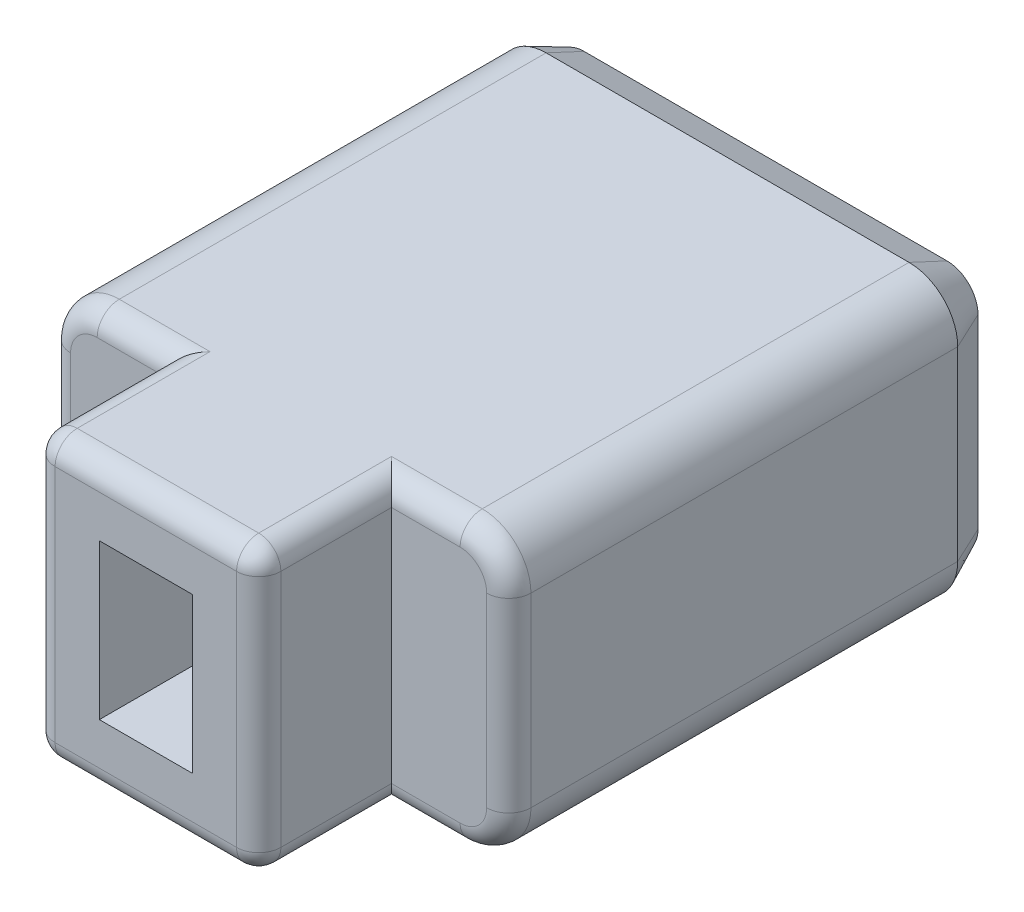
SolidWorks part; units mm, degrees
ref_plane "Plan de face" through (0, 0, 0) normal (0, 0, 1) x (1, 0, 0)
ref_plane "Plan de dessus" through (0, 0, 0) normal (0, 1, 0) x (1, 0, 0)
ref_plane "Plan de droite" through (0, 0, 0) normal (1, 0, 0) x (0, 0, -1)
sketch "Esquisse2" plane through (0, 0, 0) normal (0, 0, 1) x (1, 0, 0)
  line L1 (1.1, 0) -> (9.3, 0)
  line L2 (0, 1.1) -> (0, 5.3)
  line L3 (1.1, 6.4) -> (9.3, 6.4)
  line L4 (10.4, 1.1) -> (10.4, 5.3)
  arc A0 (9.3, 6.4) -> (10.4, 5.3) centre (9.3, 5.3) cw
  arc A1 (9.3, 0) -> (10.4, 1.1) centre (9.3, 1.1) ccw
  arc A2 (1.1, 0) -> (0, 1.1) centre (1.1, 1.1) cw
  arc A3 (0, 5.3) -> (1.1, 6.4) centre (1.1, 5.3) cw
  point P7 (10.4, 6.4)
  point P12 (0, 0)
  point P15 (0, 6.4)
  dimension "D3" = 1.1
  dimension "D1" = 10.4
  dimension "D2" = 6.4
extrude "Boss.-Extru.1" add sketch "Esquisse2" along normal blind 14
sketch "Esquisse3" plane through (0, 0, 14) normal (0, 0, 1) x (1, 0, 0)
  line L0 (0, 5.3) -> (0, 1.1) construction
  line L1 (4.15, 4.95) -> (6.25, 4.95)
  line L2 (4.15, 4.95) -> (4.15, 1.45)
  line L3 (4.15, 1.45) -> (6.25, 1.45)
  line L4 (6.25, 4.95) -> (6.25, 1.45)
  line L5 (10.4, 1.1) -> (10.4, 5.3) construction
  line L6 (9.3, 6.4) -> (1.1, 6.4) construction
  line L7 (1.1, 0) -> (9.3, 0) construction
  dimension "D1" = 2.1
  dimension "D2" = 3.5
  dimension "D3" = 4.15
  dimension "D4" = 4.15
  dimension "D5" = 1.45
  dimension "D6" = 1.45
extrude "Enlèv. mat.-Extru.1" cut sketch "Esquisse3" against normal blind 3
sketch "Esquisse4" plane through (0, 0, 14) normal (0, 0, 1) x (1, 0, 0)
  line L0 (2.65, 6.4) -> (2.65, 0)
  line L1 (9.3, 6.4) -> (1.1, 6.4) construction
  line L2 (1.1, 0) -> (9.3, 0) construction
  line L3 (2.65, 0) -> (7.75, 0)
  line L4 (7.75, 0) -> (7.75, 6.4)
  line L5 (7.75, 6.4) -> (2.65, 6.4)
  line L6 (4.15, 4.95) -> (4.15, 1.45) construction
  line L7 (6.25, 1.45) -> (6.25, 4.95) construction
  dimension "D1" = 1.5
  dimension "D2" = 1.5
extrude "Enlèv. mat.-Extru.2" cut sketch "Esquisse4" against normal blind 3 flip side to cut
fillet "Congé1" radius 0.5 18 edges at (8.525, 0, 11) (10.0778, 0.3222, 11) (10.4, 3.2, 11) (10.0778, 6.0778, 11) (1.875, 6.4, 11) (0.3222, 6.0778, 11) (1.875, 0, 11) (0.3222, 0.3222, 11) (7.75, 6.4, 12.5) (2.65, 6.4, 12.5) (7.75, 0, 12.5) (2.65, 0, 12.5) (2.65, 3.2, 14) (5.2, 6.4, 14) (7.75, 3.2, 14) (5.2, 0, 14) (8.525, 6.4, 11) (0, 3.2, 11)
chamfer "Chanfrein1" distance 0.4 angle 65 8 edges at (5.2, 0, 0) (10.0778, 0.3222, 0) (0.3222, 0.3222, 0) (10.4, 3.2, 0) (0, 3.2, 0) (10.0778, 6.0778, 0) (0.3222, 6.0778, 0) (5.2, 6.4, 0) first distance on face at (5.2, 3.2, 0)
sketch "Esquisse5" plane through (0, 0, 0) normal (0, 0, -1) x (-1, 0, 0)
  line L0 (-0.4, 5.3) -> (-10, 5.3) construction
  arc A0 (-9.3, 6) -> (-10, 5.3) centre (-9.3, 5.3) ccw construction
  text T0 "VFR" font "Century Gothic" height 4
extrude "Enlèv. mat.-Extru.3" cut sketch "Esquisse5" against normal blind 0.3
extrude "Boss.-Extru.2" add sketch "Esquisse5<2>" along normal blind 0.3 separate body
sketch "Esquisse5<2>" plane through (0, 0, 0) normal (0, 0, -1) x (-1, 0, 0) same geometry as "Esquisse5"
